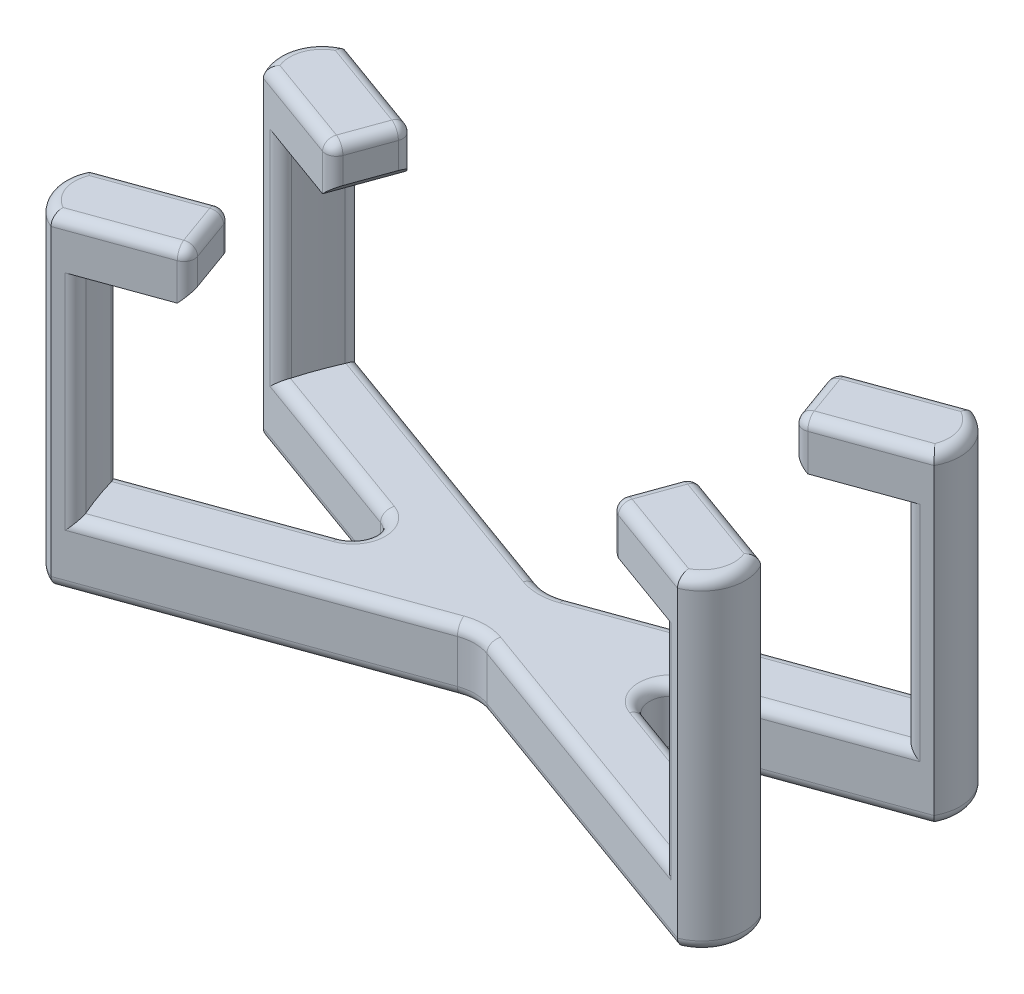
SolidWorks part; units mm, degrees
material "Custom Plastic"
ref_plane "Front Plane" through (0, 0, 0) normal (0, 0, 1) x (1, 0, 0)
ref_plane "Top Plane" through (0, 0, 0) normal (0, 1, 0) x (1, 0, 0)
ref_plane "Right Plane" through (0, 0, 0) normal (1, 0, 0) x (0, 0, -1)
sketch "Sketch1" plane through (0, 0, 0) normal (0, 1, 0) x (1, 0, 0)
  line L0 (0, -1000) -> (0, 49000) construction
  line L1 (0, 0) -> (-15.6175, -5.6458) construction
  line L2 (0, 0) -> (-15.047, 5.4395) construction
  line L3 (-15.4907, -4.0049) -> (-7.0136, -0.9404)
  line L4 (-14.4708, -6.8262) -> (-0.6799, -1.8408)
  line L5 (-15.4907, 4.0049) -> (-7.0136, 0.9404)
  line L6 (-14.4708, 6.8262) -> (-0.6799, 1.8408)
  line L7 (0, 0) -> (15.047, 5.4395) construction
  line L8 (0, 0) -> (15.6175, -5.6458) construction
  line L9 (14.4708, 6.8262) -> (0.6799, 1.8408)
  line L10 (15.4907, 4.0049) -> (7.0136, 0.9404)
  line L11 (14.4708, -6.8262) -> (0.6799, -1.8408)
  line L12 (15.4907, -4.0049) -> (7.0136, -0.9404)
  circle A0 centre (0, 0) radius 15 construction
  circle A2 centre (0, 0) radius 16 construction
  arc A3 (-15.4907, -4.0049) -> (-14.4708, -6.8262) centre (-13.7366, -4.9658) ccw
  arc A4 (-14.4708, 6.8262) -> (-15.4907, 4.0049) centre (-13.7366, 4.9658) ccw
  arc A5 (14.4708, 6.8262) -> (15.4907, 4.0049) centre (13.7366, 4.9658) cw
  arc A6 (15.4907, -4.0049) -> (14.4708, -6.8262) centre (13.7366, -4.9658) cw
  arc A7 (-7.0136, -0.9404) -> (-7.0136, 0.9404) centre (-7.3536, 0) ccw
  arc A8 (7.0136, -0.9404) -> (7.0136, 0.9404) centre (7.3536, 0) cw
  arc A9 (-0.6799, 1.8408) -> (0.6799, 1.8408) centre (0, 3.7217) ccw
  arc A10 (0.6799, -1.8408) -> (-0.6799, -1.8408) centre (0, -3.7217) ccw
  point P15 (-15.4907, -4.0049)
  point P17 (-14.4708, -6.8262)
  point P29 (14.4708, -6.8262)
  point P30 (15.4907, -4.0049)
  dimension "D2" = 30
  dimension "D1" = 32
  dimension "D3" = 2
  dimension "D4" = 2
  dimension "D9" = 1
  dimension "D10" = 2
  dimension "D11" = 2
  dimension "D5" = 140.25
  dimension "D6" = 140.25
  dimension "D7" = 3
  dimension "D8" = 3
extrude "Boss-Extrude1" add sketch "Sketch1" along normal blind 3
sketch "Sketch2" plane through (0, 3, 0) normal (0, 1, 0) x (1, 0, 0)
  line L8 (-15.4907, 4.0049) -> (-7.0136, 0.9404)
  line L9 (-7.0136, -0.9404) -> (-15.4907, -4.0049)
  line L10 (-14.4708, -6.8262) -> (-0.6799, -1.8408)
  line L11 (0.6799, -1.8408) -> (14.4708, -6.8262)
  line L12 (15.4907, -4.0049) -> (7.0136, -0.9404)
  line L13 (7.0136, 0.9404) -> (15.4907, 4.0049)
  line L14 (14.4708, 6.8262) -> (0.6799, 1.8408)
  line L15 (-0.6799, 1.8408) -> (-14.4708, 6.8262)
  line L16 (-15.4907, 4.0049) -> (-14.4985, 3.6462)
  line L17 (-14.4985, -3.6462) -> (-15.4907, -4.0049)
  line L18 (-14.4708, -6.8262) -> (-13.4786, -6.4675)
  line L19 (13.4786, -6.4675) -> (14.4708, -6.8262)
  line L20 (15.4907, -4.0049) -> (14.4985, -3.6462)
  line L21 (14.4985, 3.6462) -> (15.4907, 4.0049)
  line L22 (14.4708, 6.8262) -> (13.4786, 6.4675)
  line L23 (-13.4786, 6.4675) -> (-14.4708, 6.8262)
  arc A0 (-13.4786, 6.4675) -> (-14.4985, 3.6462) centre (0, 0) ccw
  arc A1 (14.4985, 3.6462) -> (13.4786, 6.4675) centre (0, 0) ccw
  arc A2 (13.4786, -6.4675) -> (14.4985, -3.6462) centre (0, 0) ccw
  arc A3 (-14.4985, -3.6462) -> (-13.4786, -6.4675) centre (0, 0) ccw
  arc A8 (-14.4708, 6.8262) -> (-15.4907, 4.0049) centre (-13.7366, 4.9658) ccw
  arc A9 (-7.0136, -0.9404) -> (-7.0136, 0.9404) centre (-7.3536, 0) ccw
  arc A10 (-15.4907, -4.0049) -> (-14.4708, -6.8262) centre (-13.7366, -4.9658) ccw
  arc A11 (0.6799, -1.8408) -> (-0.6799, -1.8408) centre (0, -3.7217) ccw
  arc A12 (14.4708, -6.8262) -> (15.4907, -4.0049) centre (13.7366, -4.9658) ccw
  arc A13 (7.0136, 0.9404) -> (7.0136, -0.9404) centre (7.3536, 0) ccw
  arc A14 (15.4907, 4.0049) -> (14.4708, 6.8262) centre (13.7366, 4.9658) ccw
  arc A15 (-0.6799, 1.8408) -> (0.6799, 1.8408) centre (0, 3.7217) ccw
  arc A16 (-14.4708, 6.8262) -> (-15.4907, 4.0049) centre (-13.7366, 4.9658) ccw
  arc A18 (-15.4907, -4.0049) -> (-14.4708, -6.8262) centre (-13.7366, -4.9658) ccw
  arc A20 (14.4708, -6.8262) -> (15.4907, -4.0049) centre (13.7366, -4.9658) ccw
  arc A22 (15.4907, 4.0049) -> (14.4708, 6.8262) centre (13.7366, 4.9658) ccw
  dimension "D2" = 29.9
  dimension "D1" = 0
extrude "Boss-Extrude2" add sketch "Sketch2" along normal blind 12
sketch "Sketch3" plane through (0, 15, 0) normal (0, 1, 0) x (1, 0, 0)
  line L0 (-14.4985, -3.6462) -> (-10.7368, -2.2864)
  line L1 (-7.0136, -0.9404) -> (-14.4985, -3.6462) construction
  line L2 (-10.7368, -2.2864) -> (-9.7169, -5.1077)
  line L3 (-13.4786, -6.4675) -> (-0.6799, -1.8408) construction
  line L4 (-9.7169, -5.1077) -> (-13.4786, -6.4675)
  line L5 (-1000, 0) -> (49000, 0) construction
  line L6 (-9.7169, 5.1077) -> (-13.4786, 6.4675)
  line L7 (-10.7368, 2.2864) -> (-9.7169, 5.1077)
  line L8 (-14.4985, 3.6462) -> (-10.7368, 2.2864)
  line L9 (0, -1000) -> (0, 49000) construction
  line L10 (14.4985, 3.6462) -> (10.7368, 2.2864)
  line L11 (10.7368, 2.2864) -> (9.7169, 5.1077)
  line L12 (9.7169, 5.1077) -> (13.4786, 6.4675)
  line L13 (9.7169, -5.1077) -> (13.4786, -6.4675)
  line L14 (10.7368, -2.2864) -> (9.7169, -5.1077)
  line L15 (14.4985, -3.6462) -> (10.7368, -2.2864)
  arc A0 (-14.4985, -3.6462) -> (-13.4786, -6.4675) centre (0, 0) ccw construction
  arc A1 (-14.4985, -3.6462) -> (-13.4786, -6.4675) centre (0, 0) ccw
  arc A2 (-14.4985, 3.6462) -> (-13.4786, 6.4675) centre (0, 0) cw
  arc A3 (14.4985, 3.6462) -> (13.4786, 6.4675) centre (0, 0) ccw
  arc A4 (14.4985, -3.6462) -> (13.4786, -6.4675) centre (0, 0) cw
  dimension "D1" = 4
extrude "Boss-Extrude3" add sketch "Sketch3" against normal blind 2.2
chamfer "Chamfer2" distance 0.5 angle 45 4 edges at (10.2268, 12.8, 3.697) (10.2268, 12.8, -3.697) (-10.2268, 12.8, -3.697) (-10.2268, 12.8, 3.697)
fillet "Fillet1" radius 0.5 16 edges at (-11.2522, 0, -2.4727) (-6.3536, 0, 0) (-11.2522, 0, 2.4727) (-15.6175, 0, 5.6458) (-7.5753, 0, 4.3335) (0, 0, 1.7217) (7.5753, 0, 4.3335) (15.6175, 0, 5.6458) (11.2522, 0, 2.4727) (6.3536, 0, 0) (11.2522, 0, -2.4727) (15.6175, 0, -5.6458) (7.5753, 0, -4.3335) (0, 0, -1.7217) (-7.5753, 0, -4.3335) (-15.6175, 0, -5.6458)
fillet "Fillet2" radius 0.5 16 edges at (-13.1137, 15, 3.1456) (-10.2268, 15, 3.697) (-12.0938, 15, 5.9669) (-15.6175, 15, 5.6458) (-12.0938, 15, -5.9669) (-10.2268, 15, -3.697) (-13.1137, 15, -3.1456) (-15.6175, 15, -5.6458) (15.6175, 15, -5.6458) (13.1137, 15, -3.1456) (10.2268, 15, -3.697) (12.0938, 15, -5.9669) (15.6175, 15, 5.6458) (12.0938, 15, 5.9669) (10.2268, 15, 3.697) (13.1137, 15, 3.1456)
fillet "Fillet3" radius 0.5 16 edges at (9.9044, 14.8536, 5.0197) (10.8247, 14.8536, 2.4739) (10.8247, 14.8536, -2.4739) (9.9044, 14.8536, -5.0197) (-9.9044, 14.8536, 5.0197) (-10.8247, 14.8536, 2.4739) (-9.9044, 14.8536, -5.0197) (-10.8247, 14.8536, -2.4739) (9.7169, 13.9, 5.1077) (10.7368, 13.9, 2.2864) (10.7368, 13.9, -2.2864) (9.7169, 13.9, -5.1077) (-9.7169, 13.9, 5.1077) (-10.7368, 13.9, 2.2864) (-9.7169, 13.9, -5.1077) (-10.7368, 13.9, -2.2864)
fillet "Fillet4" radius 0.5 8 edges at (13.4786, 7.9, 6.4675) (14.4985, 7.9, 3.6462) (14.4985, 7.9, -3.6462) (13.4786, 7.9, -6.4675) (-13.4786, 7.9, 6.4675) (-14.4985, 7.9, 3.6462) (-13.4786, 7.9, -6.4675) (-14.4985, 7.9, -3.6462)
fillet "Fillet5" radius 0.5 12 edges at (7.3346, 3, -4.2465) (-7.3346, 3, -4.2465) (11.0114, 3, 2.3856) (11.0114, 3, -2.3856) (7.3346, 3, 4.2465) (0, 3, 1.7217) (-11.0114, 3, 2.3856) (-6.3536, 3, 0) (0, 3, -1.7217) (6.3536, 3, 0) (-7.3346, 3, 4.2465) (-11.0114, 3, -2.3856)
